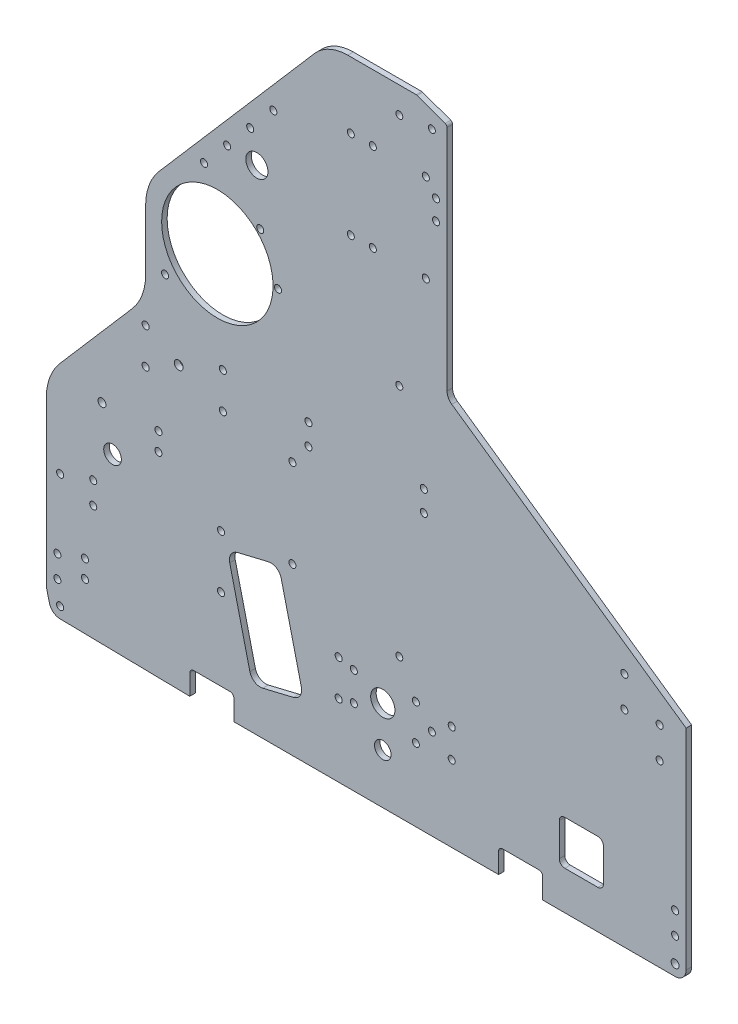
SolidWorks part; units mm, degrees
ref_plane "Front Plane" through (0, 0, 0) normal (0, 0, 1) x (1, 0, 0)
ref_plane "Top Plane" through (0, 0, 0) normal (0, 1, 0) x (1, 0, 0)
ref_plane "Right Plane" through (0, 0, 0) normal (1, 0, 0) x (0, 0, -1)
sketch "Sketch1" plane through (0, 0, 0) normal (0, 0, 1) x (1, 0, 0)
  line L0 (82.55, -20.32) -> (82.55, -6.35)
  line L2 (0, 0) -> (0, 157.48)
  line L4 (368.3, -20.32) -> (368.3, 106.68)
  line L5 (82.55, -6.35) -> (107.95, -6.35)
  line L6 (107.95, -6.35) -> (107.95, -20.32)
  line L7 (107.95, -20.32) -> (260.35, -20.32)
  line L8 (260.35, -20.32) -> (260.35, -6.35)
  line L9 (260.35, -6.35) -> (285.75, -6.35)
  line L10 (285.75, -6.35) -> (285.75, -20.32)
  line L11 (285.75, -20.32) -> (368.3, -20.32)
  line L12 (361.95, 12.7) -> (368.3, 12.7) construction
  line L13 (0, 0) -> (6.35, 0) construction
  line L14 (0.1896, -7.8901) -> (1.7771, -14.2401)
  line L15 (7.8295, -19.0491) -> (82.55, -20.32)
  line L16 (0, 0) -> (0, -6.35)
  line L17 (76.2, 141.605) -> (79.375, 141.605) construction
  line L18 (57.15, 131.2863) -> (101.6, 131.2862) construction
  line L19 (57.15, 131.2863) -> (57.15, 151.9238) construction
  line L20 (101.6, 131.2862) -> (101.6, 151.9237) construction
  line L21 (57.15, 151.9238) -> (101.6, 151.9237) construction
  line L22 (57.15, 131.2863) -> (101.6, 151.9237) construction
  line L23 (101.6, 131.2862) -> (57.15, 151.9238) construction
  line L25 (203.2, 59.805) -> (203.2, 194.805) construction
  line L26 (203.2, 194.805) -> (203.2, 329.805) construction
  line L27 (355.6, 332.105) -> (330.2, 332.105) construction
  line L28 (330.2, 332.105) -> (330.2, 217.805) construction
  line L29 (330.2, 217.805) -> (355.6, 217.805) construction
  line L30 (355.6, 217.805) -> (355.6, 332.105) construction
  line L31 (203.2, 344.805) -> (203.2, 194.805) construction
  line L32 (50.8, 332.105) -> (76.2, 332.105) construction
  line L33 (76.2, 332.105) -> (76.2, 217.805) construction
  line L34 (50.8, 217.805) -> (50.8, 332.105) construction
  line L35 (76.2, 217.805) -> (50.8, 217.805) construction
  line L36 (213.2, 344.805) -> (230.6638, 338.455)
  line L37 (203.2, 344.805) -> (161.925, 344.805)
  line L38 (203.2, 344.805) -> (213.2, 344.805)
  line L39 (348.5362, 344.805) -> (413.4623, 344.805)
  line L40 (348.5362, 344.805) -> (230.6638, 344.805) construction
  line L42 (161.925, 344.805) -> (0, 157.48)
  line L44 (230.6638, 338.455) -> (230.6638, 202.565)
  line L45 (230.6638, 202.565) -> (368.3, 106.68)
  line L46 (213.2, 344.805) -> (-141.0713, 344.805) construction
  circle A0 centre (6.35, 0) radius 2.032
  circle A1 centre (6.35, 12.7) radius 2.032
  circle A2 centre (361.95, 0) radius 2.032
  circle A3 centre (361.95, 12.7) radius 2.032
  arc A5 (1.7771, -14.2401) -> (7.8295, -19.0491) centre (7.9375, -12.7) ccw
  circle A6 centre (7.9375, -12.7) radius 2.032
  arc A7 (0, -6.35) -> (0.1896, -7.8901) centre (6.35, -6.35) ccw
  circle A8 centre (38.1, 78.105) radius 5.08
  circle A9 centre (76.2, 141.605) radius 2.54
  circle A10 centre (101.6, 131.2862) radius 2.032
  circle A11 centre (101.6, 151.9237) radius 2.032
  circle A12 centre (57.15, 151.9238) radius 2.032
  circle A13 centre (57.15, 131.2863) radius 2.032
  circle A15 centre (203.2, 59.805) radius 2
  circle A16 centre (203.2, 194.805) radius 2
  circle A17 centre (203.2, 329.805) radius 2
  circle A18 centre (63.5, 313.055) radius 2.032
  circle A20 centre (355.6, 332.105) radius 2.032
  circle A21 centre (330.2, 332.105) radius 2.032
  circle A22 centre (355.6, 217.805) radius 2.032
  circle A23 centre (330.2, 217.805) radius 2.032
  circle A24 centre (50.8, 332.105) radius 2.032
  circle A25 centre (76.2, 332.105) radius 2.032
  circle A26 centre (50.8, 217.805) radius 2.032
  circle A27 centre (76.2, 217.805) radius 2.032
  circle A28 centre (221.9319, 332.105) radius 2
  circle A29 centre (224.3138, 298.831) radius 2.032
  circle A30 centre (353.06, 100.7351) radius 2.032
  circle A31 centre (332.74, 115.9751) radius 2.032
  circle A32 centre (332.74, 98.1951) radius 2.032
  circle A33 centre (353.06, 82.9551) radius 2.032
  circle A34 centre (117.3562, 280.4276) radius 2.032
  circle A35 centre (104.0678, 265.0548) radius 2.032
  circle A36 centre (90.7795, 249.682) radius 2.032
  circle A38 centre (130.6445, 295.8004) radius 2.032
  circle A39 centre (68.326, 182.9237) radius 2.032
  circle A40 centre (224.3138, 287.401) radius 2.032
  point P82 (203.2, 344.805)
  point P83 (221.9319, 341.63)
  point P90 (368.3, 62.484)
  dimension "D6" = 4.064
  dimension "D10" = 6.35
  dimension "D11" = 4.064
  dimension "D17" = 38.1
  dimension "D27" = 4
  dimension "D31" = 4.064
  dimension "D32" = 41.275
  dimension "D36" = 4.064
  dimension "D47" = 39.624
  dimension "D48" = 4.064
  dimension "D25" = 5.08
  dimension "D26" = 4.064
  dimension "D52" = 4.064
  dimension "D65" = 4.064
  dimension "D69" = 10.16
  dimension "D2" = 127
  dimension "D3" = 13.97
  dimension "D4" = 25.4
  dimension "D5" = 152.4
  dimension "D7" = 12.7
  dimension "D8" = 6.35
  dimension "D9" = 20.32
  dimension "D12" = 12.7
  dimension "D13" = 1.5875
  dimension "D14" = 82.55
  dimension "D15" = 368.3
  dimension "D16" = 6.35
  dimension "D18" = 98.425
  dimension "D19" = 38.1
  dimension "D20" = 63.5
  dimension "D21" = 3.175
  dimension "D22" = 270
  dimension "D23" = 20.6375
  dimension "D24" = 44.45
  dimension "D28" = 135
  dimension "D29" = 12.7
  dimension "D30" = 15
  dimension "D33" = 63.5
  dimension "D34" = 27.4638
  dimension "D35" = 12.7
  dimension "D37" = 114.3
  dimension "D38" = 25.4
  dimension "D39" = 12.7
  dimension "D40" = 157.48
  dimension "D41" = 142.24
  dimension "D42" = 365.125
  dimension "D43" = 10
  dimension "D44" = 6.35
  dimension "D45" = 31.75
  dimension "D46" = 6.35
  dimension "D49" = 6.35
  dimension "D50" = 203.2
  dimension "D51" = 15.24
  dimension "D53" = 17.78
  dimension "D54" = 17.78
  dimension "D55" = 20.32
  dimension "D56" = 15.24
  dimension "D57" = 92.202
  dimension "D58" = 8.382
  dimension "D59" = 20.32
  dimension "D60" = 20.32
  dimension "D61" = 8.382
  dimension "D62" = 20.32
  dimension "D63" = 8.382
  dimension "D64" = 8.382
  dimension "D66" = 35.052
  dimension "D67" = 68.326
  dimension "D68" = 11.43
extrude "Boss-Extrude1" add sketch "Sketch1" along normal blind 3.175 contours L16 A7 L14 A5 L15 L2 A0 A1 A6 region at (171.4477, 119.555, 0)
fillet "Fillet1" radius 2.286 4 edges at (285.75, -6.35, 1.5875) (107.95, -6.35, 1.5875) (260.35, -6.35, 1.5875) (82.55, -6.35, 1.5875)
fillet "Fillet2" radius 6.35 1 edges at (230.6638, 202.565, 1.5875)
sketch "Sketch2" plane through (0, 0, 0) normal (0, 0, -1) x (-1, 0, 0)
  circle A0 centre (-100.5528, 71.086) radius 2.032 construction
  circle A1 centre (-100.5528, 40.606) radius 2.032 construction
  circle A2 centre (-22.225, 18.2025) radius 2.032 construction
  circle A3 centre (-22.225, 8.0425) radius 2.032 construction
  circle A4 centre (-100.5528, 71.086) radius 2.032
  circle A5 centre (-100.5528, 40.606) radius 2.032
  circle A6 centre (-22.225, 18.2025) radius 2.032
  circle A7 centre (-22.225, 8.0425) radius 2.032
extrude "Cut-Extrude1" cut sketch "Sketch2" against normal through all
fillet "Fillet3" radius 1.5875 2 edges at (230.6638, 338.455, 1.5875) (213.2, 344.805, 1.5875)
sketch "Sketch3" plane through (0, 0, 3.175) normal (0, 0, 1) x (1, 0, 0)
  line L0 (132.9524, 63.2646) -> (132.7215, 64.2281) construction
  line L1 (128.3814, 66.8897) -> (110.6828, 62.6472) construction
  line L2 (114.5132, 58.4237) -> (126.8822, 61.3887) construction
  line L3 (108.0212, 58.3071) -> (108.2522, 57.3436) construction
  line L4 (131.2006, 57.703) -> (140.0164, 20.9265) construction
  line L5 (144.0993, 16.7636) -> (132.9524, 63.2646) construction
  line L6 (108.2522, 57.3436) -> (119.3991, 10.8426) construction
  line L7 (121.1509, 16.4042) -> (112.3351, 53.1807) construction
  line L8 (119.3991, 10.8426) -> (119.6301, 9.8791) construction
  line L9 (144.3303, 15.8001) -> (144.0993, 16.7636) construction
  line L10 (137.8383, 15.6835) -> (125.4694, 12.7185) construction
  line L11 (123.9701, 7.2175) -> (141.6687, 11.4601) construction
  line L12 (132.9524, 63.2646) -> (132.7215, 64.2281)
  line L13 (128.3814, 66.8897) -> (110.6828, 62.6472)
  line L14 (114.5132, 58.4237) -> (126.8822, 61.3887)
  line L15 (108.0212, 58.3071) -> (108.2522, 57.3436)
  line L16 (131.2006, 57.703) -> (140.0164, 20.9265)
  line L17 (144.0993, 16.7636) -> (132.9524, 63.2646)
  line L18 (108.2522, 57.3436) -> (119.3991, 10.8426)
  line L19 (121.1509, 16.4042) -> (112.3351, 53.1807)
  line L20 (119.3991, 10.8426) -> (119.6301, 9.8791)
  line L21 (144.3303, 15.8001) -> (144.0993, 16.7636)
  line L22 (137.8383, 15.6835) -> (125.4694, 12.7185)
  line L23 (123.9701, 7.2175) -> (141.6687, 11.4601)
  line L24 (127.7894, 69.3598) -> (110.0908, 65.1172)
  line L25 (105.5512, 57.715) -> (105.7822, 56.7515)
  line L26 (105.7822, 56.7515) -> (116.9291, 10.2505)
  line L27 (116.9291, 10.2505) -> (117.16, 9.287)
  line L28 (124.5622, 4.7475) -> (142.2608, 8.99)
  line L29 (146.8003, 16.3922) -> (146.5694, 17.3557)
  line L30 (146.5694, 17.3557) -> (135.4225, 63.8567)
  line L31 (135.4225, 63.8567) -> (135.1915, 64.8202)
  line L32 (14.605, -0.1369) -> (103.7278, 32.3011) construction
  line L33 (14.605, -0.1369) -> (103.7278, 32.3011)
  line L34 (0, -6.35) -> (0, 157.48) construction
  line L35 (-39.6666, 74.7152) -> (103.7278, 126.9065) construction
  line L36 (26.9875, 46.9531) -> (26.9875, 59.6531) construction
  line L37 (107.95, -20.32) -> (260.35, -20.32) construction
  line L38 (64.5259, 92.5258) -> (64.5259, 102.9405) construction
  arc A0 (132.7215, 64.2281) -> (128.6308, 66.9403) centre (129.2206, 63.3889) ccw construction
  arc A1 (110.6828, 62.6472) -> (110.4377, 62.5791) centre (111.522, 59.1463) ccw construction
  arc A2 (128.6308, 66.9403) -> (128.3814, 66.8897) centre (129.2206, 63.3889) ccw construction
  arc A3 (110.4377, 62.5791) -> (108.0212, 58.3071) centre (111.522, 59.1463) ccw construction
  arc A4 (119.6301, 9.8791) -> (123.7207, 7.1669) centre (123.1309, 10.7183) ccw construction
  arc A5 (141.9139, 11.5281) -> (144.3303, 15.8001) centre (140.8295, 14.9609) ccw construction
  arc A6 (141.6687, 11.4601) -> (141.9139, 11.5281) centre (140.8295, 14.9609) ccw construction
  arc A7 (123.7207, 7.1669) -> (123.9701, 7.2175) centre (123.1309, 10.7183) ccw construction
  arc A8 (132.7215, 64.2281) -> (128.6308, 66.9403) centre (129.2206, 63.3889) ccw
  arc A9 (110.6828, 62.6472) -> (110.4377, 62.5791) centre (111.522, 59.1463) ccw
  arc A10 (128.6308, 66.9403) -> (128.3814, 66.8897) centre (129.2206, 63.3889) ccw
  arc A11 (110.4377, 62.5791) -> (108.0212, 58.3071) centre (111.522, 59.1463) ccw
  arc A12 (119.6301, 9.8791) -> (123.7207, 7.1669) centre (123.1309, 10.7183) ccw
  arc A13 (141.9139, 11.5281) -> (144.3303, 15.8001) centre (140.8295, 14.9609) ccw
  arc A14 (141.6687, 11.4601) -> (141.9139, 11.5281) centre (140.8295, 14.9609) ccw
  arc A15 (123.7207, 7.1669) -> (123.9701, 7.2175) centre (123.1309, 10.7183) ccw
  arc A16 (110.0908, 65.1172) -> (109.6726, 65.0012) centre (111.522, 59.1463) ccw
  arc A17 (109.6726, 65.0012) -> (105.5512, 57.715) centre (111.522, 59.1463) ccw
  arc A18 (117.16, 9.287) -> (124.1369, 4.6613) centre (123.1309, 10.7183) ccw
  arc A19 (124.1369, 4.6613) -> (124.5622, 4.7475) centre (123.1309, 10.7183) ccw
  arc A20 (142.2608, 8.99) -> (142.6789, 9.1061) centre (140.8295, 14.9609) ccw
  arc A21 (142.6789, 9.1061) -> (146.8003, 16.3922) centre (140.8295, 14.9609) ccw
  arc A22 (135.1915, 64.8202) -> (128.2147, 69.446) centre (129.2206, 63.3889) ccw
  arc A23 (128.2147, 69.446) -> (127.7894, 69.3598) centre (129.2206, 63.3889) ccw
  circle A26 centre (133.35, 208.2281) radius 2.032 construction
  circle A33 centre (26.9875, 46.9531) radius 2.032
  circle A34 centre (26.9875, 59.6531) radius 2.032
  circle A35 centre (7.9375, 53.3031) radius 2.032
  circle A37 centre (32.0306, 100.8109) radius 31.75 construction
  circle A38 centre (32.0306, 100.8109) radius 2.286
  circle A39 centre (123.1207, 232.9238) radius 2.032 construction
  circle A40 centre (64.5259, 102.9405) radius 2.032
  circle A41 centre (64.5259, 92.5258) radius 2.032
  circle A42 centre (133.35, 208.2281) radius 2.032
  circle A43 centre (123.1207, 232.9238) radius 2.032
  ellipse E0 centre (124.5974, 48.8487) end of major axis (128.5376, 61.3578) minor radius 6 (131.2006, 57.703) -> (126.8822, 61.3887) ccw construction
  ellipse E1 centre (122.2349, 48.2824) end of major axis (113.0518, 57.6456) minor radius 6 (114.5132, 58.4237) -> (112.3351, 53.1807) ccw construction
  ellipse E2 centre (127.7541, 25.2585) end of major axis (131.6942, 37.7675) minor radius 6 (121.1509, 16.4042) -> (125.4694, 12.7185) ccw construction
  ellipse E3 centre (130.1166, 25.8248) end of major axis (139.2998, 16.4616) minor radius 6 (137.8383, 15.6835) -> (140.0164, 20.9265) ccw construction
  ellipse E4 centre (124.5974, 48.8487) end of major axis (120.6573, 36.3397) minor radius 6 (131.2006, 57.703) -> (126.8822, 61.3887) ccw
  ellipse E5 centre (122.2349, 48.2824) end of major axis (131.4181, 38.9192) minor radius 6 (114.5132, 58.4237) -> (112.3351, 53.1807) ccw
  ellipse E6 centre (127.7541, 25.2585) end of major axis (131.6942, 37.7675) minor radius 6 (121.1509, 16.4042) -> (125.4694, 12.7185) ccw
  ellipse E7 centre (130.1166, 25.8248) end of major axis (139.2998, 16.4616) minor radius 6 (137.8383, 15.6835) -> (140.0164, 20.9265) ccw
  point P93 (26.9875, 53.3031)
  point P115 (32.0306, 100.8109)
  dimension "D3" = 63.5
  dimension "D4" = 4.572
  dimension "D8" = 4.064
  dimension "D2" = 88.9
  dimension "D5" = 7.9375
  dimension "D6" = 19.05
  dimension "D7" = 73.6231
  dimension "D9" = 12.7
  dimension "D10" = 10.4147
  dimension "D11" = 37.5384
  dimension "D12" = 45.5727
  dimension "D1" = 2.54
extrude "Cut-Extrude2" cut sketch "Sketch3" against normal through all contours A22 A23 L24 A16 A17 L25 L26 L27 A18 A19 L28 A20 A21 L29 L30 L31 A15 A12 L20 L18 L15 A11 A9 L13 A10 A8 L12 L17 L21 A13 A14 L23 | A12 A15 L23 A14 A13 L21 L17 L12 A8 A10 L13 A9 A11 L15 L18 L20 E7 L22 E6 L19 E5 L14 E4 L16 | L22 E7 L16 E4 L14 E5 L19 E6 | A38 | A41 | A40 | A35 | A34 | A33 | A43 | A42 region at (137.844, 39.8506, 3.175) region at (126.1758, 37.0536, 3.175) region at (128.1544, 68.6507, 3.175) region at (32.0306, 100.8109, 3.175) region at (64.5259, 102.9405, 3.175) region at (64.5259, 92.5258, 3.175)
sketch "Sketch4" plane through (0, 0, 3.175) normal (0, 0, 1) x (1, 0, 0)
  line L0 (57.15, 151.9238) -> (101.6, 151.9237) construction
  line L1 (168.275, 21.4312) -> (212.725, 21.4312) construction
  line L2 (168.275, 21.4312) -> (168.275, 42.0687) construction
  line L3 (168.275, 42.0687) -> (212.725, 42.0687) construction
  line L4 (212.725, 21.4312) -> (212.725, 42.0687) construction
  line L5 (168.275, 21.4312) -> (212.725, 42.0687) construction
  line L6 (168.275, 42.0687) -> (212.725, 21.4312) construction
  line L7 (57.15, 131.2863) -> (57.15, 151.9238) construction
  line L8 (107.95, -20.32) -> (260.35, -20.32) construction
  line L9 (193.675, 31.75) -> (177.005, 31.75) construction
  line L10 (190.5, 31.75) -> (193.675, 31.75) construction
  line L11 (6.35, 12.7) -> (361.95, 12.7) construction
  line L12 (107.95, -6.35) -> (107.95, -20.32) construction
  line L13 (193.675, 31.75) -> (220.6625, 31.75) construction
  line L14 (177.005, 23.4569) -> (177.005, 40.0431) construction
  line L15 (213.2, 44.805) -> (193.2, 44.805) construction
  line L16 (213.2, 44.805) -> (213.2, 344.805) construction
  line L17 (213.2, 344.805) -> (193.2, 344.805) construction
  line L18 (193.2, 44.805) -> (193.2, 344.805) construction
  line L19 (213.2, 44.805) -> (193.2, 344.805) construction
  line L20 (213.2, 344.805) -> (193.2, 44.805) construction
  line L21 (226.9319, 332.105) -> (226.9319, 31.75) construction
  line L22 (237.33, 40.0431) -> (233.3612, 40.0431) construction
  line L23 (237.33, 23.4569) -> (233.3612, 23.4569) construction
  circle A0 centre (168.275, 42.0687) radius 2.032
  circle A1 centre (212.725, 42.0687) radius 2.032
  circle A2 centre (212.725, 21.4312) radius 2.032
  circle A3 centre (168.275, 21.4312) radius 2.032
  circle A4 centre (193.675, 31.75) radius 6.985
  circle A7 centre (220.6625, 31.75) radius 14.2875 construction
  circle A8 centre (193.675, 31.75) radius 12.7 construction
  circle A9 centre (177.005, 40.0431) radius 2.032
  circle A10 centre (177.005, 23.4569) radius 2.032
  circle A11 centre (237.33, 40.0431) radius 2.032 construction
  circle A12 centre (237.33, 23.4569) radius 2.032 construction
  circle A13 centre (193.675, 8.4667) radius 4.7625
  circle A14 centre (221.9319, 31.75) radius 2.032
  circle A15 centre (221.9319, 31.75) radius 5 construction
  circle A16 centre (221.9319, 332.105) radius 5 construction
  circle A17 centre (233.3612, 23.4569) radius 2.032
  circle A18 centre (233.3612, 40.0431) radius 2.032
  point P0 (190.5, 31.75)
  point P26 (203.2, 194.805)
  point P38 (177.005, 31.75)
  dimension "D1" = 4.064
  dimension "D4" = 13.97
  dimension "D7" = 9.525
  dimension "D10" = 25.4
  dimension "D11" = 28.575
  dimension "D16" = 10
  dimension "D17" = 4.064
  dimension "D18" = 10
  dimension "D2" = 52.07
  dimension "D3" = 3.175
  dimension "D5" = 82.55
  dimension "D6" = 26.9875
  dimension "D8" = 20
  dimension "D9" = 300
  dimension "D12" = 16.67
  dimension "D13" = 16.5862
  dimension "D14" = 60.325
  dimension "D15" = 23.2833
  dimension "D19" = 3.9688
extrude "Cut-Extrude3" cut sketch "Sketch4" against normal through all
sketch "Sketch5" plane through (0, 0, 0) normal (0, 0, -1) x (-1, 0, 0)
  line L0 (-57.15, 223.5947) -> (-57.15, 165.3337)
  line L1 (-161.925, 344.805) -> (-52.7201, 218.4699) construction
  line L2 (-57.15, 165.3337) -> (0, 99.219)
  line L3 (0, -6.35) -> (0, 157.48) construction
  line L5 (-50.4199, 215.8089) -> (0, 157.48) construction
  line L6 (-57.15, 223.5947) -> (0, 157.48)
  line L7 (0, 157.48) -> (0, 99.219)
  line L8 (-361.95, -13.97) -> (-368.3, -13.97) construction
  line L9 (-361.95, -13.97) -> (-361.95, -20.32) construction
  line L10 (-285.75, -20.32) -> (-368.3, -20.32) construction
  line L11 (-368.3, -20.32) -> (-368.3, 106.68) construction
  circle A0 centre (-98.425, 208.2281) radius 32.0675
  circle A2 centre (-361.95, -13.97) radius 2.286
  dimension "D3" = 64.135
  dimension "D7" = 4.572
  dimension "D1" = 38.1
  dimension "D2" = 57.15
  dimension "D4" = 41.275
  dimension "D5" = 41.275
  dimension "D6" = 6.35
extrude "Cut-Extrude5" cut sketch "Sketch5" against normal through all contours A0 | L7 L6 L0 L2 | A2 region at (28.575, 161.4068, 0) region at (98.425, 208.2281, 0)
fillet "Fillet4" radius 31.75 3 edges at (0, 99.219, 1.5875) (57.15, 165.3337, 1.5875) (57.15, 223.5947, 1.5875)
sketch "Sketch6" plane through (0, 0, 3.175) normal (0, 0, 1) x (1, 0, 0)
  line L0 (285.75, -20.32) -> (368.3, -20.32) construction
  line L1 (298.45, 27.305) -> (317.5, 27.305)
  line L2 (295.275, 24.13) -> (295.275, 5.08)
  line L3 (298.45, 1.905) -> (317.5, 1.905)
  line L4 (320.675, 24.13) -> (320.675, 5.08)
  line L5 (295.275, 27.305) -> (320.675, 1.905) construction
  line L6 (295.275, 1.905) -> (320.675, 27.305) construction
  line L7 (368.3, -20.32) -> (368.3, 106.68) construction
  arc A0 (295.275, 5.08) -> (298.45, 1.905) centre (298.45, 5.08) ccw
  arc A1 (317.5, 1.905) -> (320.675, 5.08) centre (317.5, 5.08) ccw
  arc A2 (317.5, 27.305) -> (320.675, 24.13) centre (317.5, 24.13) cw
  arc A3 (298.45, 27.305) -> (295.275, 24.13) centre (298.45, 24.13) ccw
  point P0 (307.975, 14.605)
  dimension "D2" = 3.175
  dimension "D1" = 25.4
  dimension "D3" = 22.225
  dimension "D4" = 47.625
extrude "Cut-Extrude6" cut sketch "Sketch6" against normal through all
fillet "Fillet5" radius 25.4 1 edges at (161.925, 344.805, 1.5875)
sketch "Sketch8" plane through (0, 0, 0) normal (0, 0, -1) x (-1, 0, 0)
  circle A0 centre (-187.96, 306.705) radius 2.032 construction
  arc A1 (-176.3652, 304.9998) -> (-176.3652, 308.4102) centre (-175.26, 306.705) ccw construction
  arc A2 (-219.0586, 304.7695) -> (-219.0586, 308.6405) centre (-218.44, 306.705) ccw construction
  circle A3 centre (-205.74, 306.705) radius 2.032 construction
  arc A4 (-219.0586, 253.9695) -> (-219.0586, 257.8405) centre (-218.44, 255.905) ccw construction
  circle A5 centre (-205.74, 255.905) radius 2.032 construction
  circle A6 centre (-187.96, 255.905) radius 2.032 construction
  arc A7 (-176.3652, 254.1998) -> (-176.3652, 257.6102) centre (-175.26, 255.905) ccw construction
  circle A8 centre (-187.96, 306.705) radius 2.032
  arc A9 (-176.3652, 304.9998) -> (-176.3652, 308.4102) centre (-175.26, 306.705) ccw
  arc A10 (-219.0586, 304.7695) -> (-219.0586, 308.6405) centre (-218.44, 306.705) ccw
  circle A11 centre (-205.74, 306.705) radius 2.032
  arc A12 (-219.0586, 253.9695) -> (-219.0586, 257.8405) centre (-218.44, 255.905) ccw
  circle A13 centre (-205.74, 255.905) radius 2.032
  circle A14 centre (-187.96, 255.905) radius 2.032
  arc A15 (-176.3652, 254.1998) -> (-176.3652, 257.6102) centre (-175.26, 255.905) ccw
  circle A16 centre (-218.44, 306.705) radius 2.032
  circle A17 centre (-175.26, 306.705) radius 2.032
  circle A18 centre (-175.26, 255.905) radius 2.032
  circle A19 centre (-218.44, 255.905) radius 2.032
  circle A20 centre (-218.44, 306.705) radius 3.9688
  circle A21 centre (-205.74, 306.705) radius 3.9688
  circle A22 centre (-175.26, 306.705) radius 3.9687
  circle A23 centre (-218.44, 255.905) radius 3.9688
  circle A24 centre (-205.74, 255.905) radius 3.9688
  circle A25 centre (-187.96, 255.905) radius 3.9687
  circle A26 centre (-175.26, 255.905) radius 3.9687
  circle A27 centre (-187.96, 306.705) radius 3.9687
  dimension "D1" = 7.9375
extrude "Cut-Extrude7" cut sketch "Sketch8" against normal through all contours A10 A16 | A9 A17 | A15 A18 | A12 A19 | A8 | A14 region at (175.26, 306.705, 0) region at (218.44, 306.705, 0) region at (218.44, 255.905, 0) region at (175.26, 255.905, 0)
sketch "Sketch10" plane through (0, 0, 3.175) normal (0, 0, 1) x (1, 0, 0)
  circle A4 centre (141.6425, 75.1606) radius 2.032 construction
  circle A5 centre (141.6425, 125.9606) radius 2.032 construction
  circle A6 centre (141.6425, 75.1606) radius 2.032
  circle A7 centre (141.6425, 125.9606) radius 2.032
extrude "Cut-Extrude8" cut sketch "Sketch10" against normal through all
fillet "Fillet6" radius 6.35 1 edges at (368.3, -20.32, 1.5875)
sketch "Sketch11" plane through (0, 0, 3.175) normal (0, 0, 1) x (1, 0, 0)
  ellipse E4 centre (150.8814, 138.43) end of major axis (150.8814, 140.462) minor radius 2.032
  ellipse E5 centre (150.8814, 150.495) end of major axis (150.8814, 152.527) minor radius 2.032
  ellipse E6 centre (217.3024, 150.495) end of major axis (217.3024, 152.527) minor radius 2.032
  ellipse E7 centre (217.3024, 138.43) end of major axis (217.3024, 140.462) minor radius 2.032
extrude "Cut-Extrude9" cut sketch "Sketch11" against normal through all
sketch "Sketch12" plane through (0, 0, 3.175) normal (0, 0, 1) x (1, 0, 0)
  line L0 (130.6445, 295.8004) -> (121.1847, 263.6885) construction
  line L1 (121.1847, 263.6885) -> (90.7795, 249.682) construction
  line L2 (154.3272, 336.0154) -> (64.88, 232.5373) construction
  line L4 (114.8255, 263.226) -> (120.7222, 270.0477) construction
  line L5 (114.8255, 263.226) -> (121.6472, 257.3293) construction
  line L6 (121.6472, 257.3293) -> (127.5439, 264.151) construction
  line L7 (120.7222, 270.0477) -> (127.5439, 264.151) construction
  line L8 (114.8255, 263.226) -> (127.5439, 264.151) construction
  line L9 (121.6472, 257.3293) -> (120.7222, 270.0477) construction
  circle A0 centre (121.1847, 263.6885) radius 6.376
  dimension "D1" = 22.225
  dimension "D2" = 9.017
extrude "Cut-Extrude10" cut sketch "Sketch12" against normal through all
